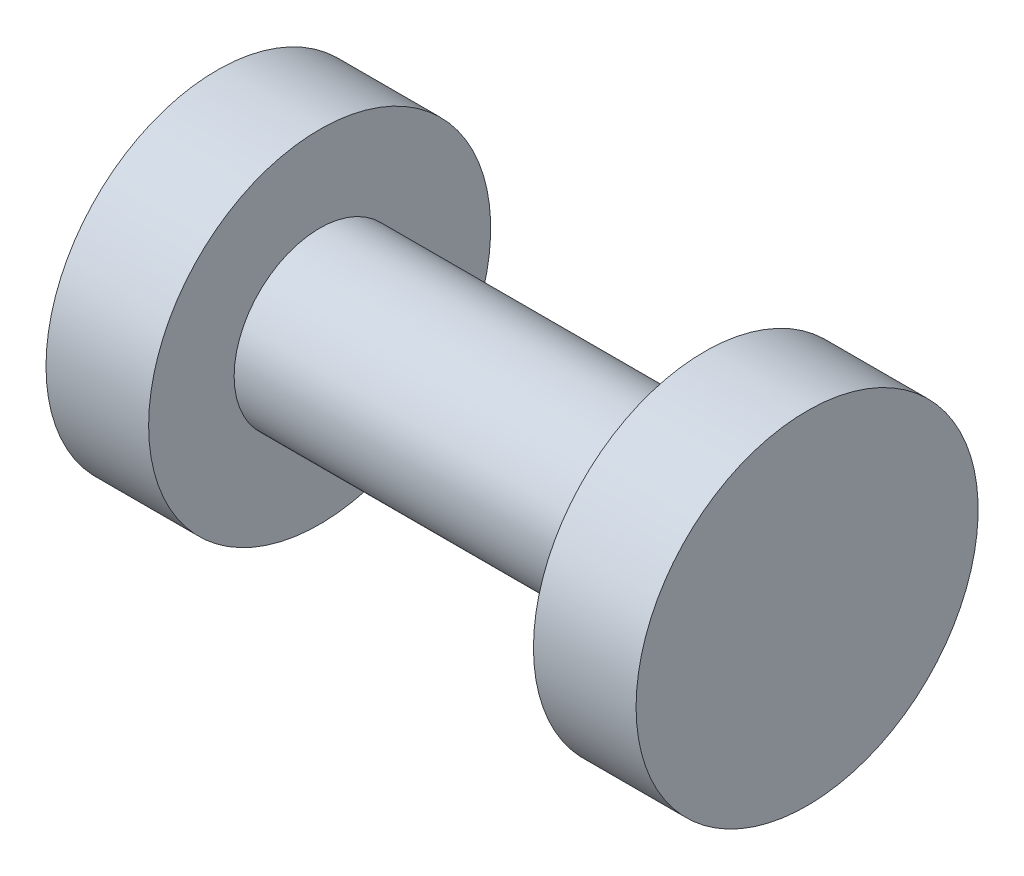
SolidWorks part; units mm, degrees
ref_plane "Front Plane" through (0, 0, 0) normal (0, 0, 1) x (1, 0, 0)
ref_plane "Top Plane" through (0, 0, 0) normal (0, 1, 0) x (1, 0, 0)
ref_plane "Right Plane" through (0, 0, 0) normal (1, 0, 0) x (0, 0, -1)
sketch "Sketch1" plane through (0, 0, 0) normal (0, 1, 0) x (1, 0, 0)
  line L0 (-10.9538, 6.35) -> (-7.1437, 6.35)
  line L1 (-7.1437, 6.35) -> (-7.1438, 3.175)
  line L2 (-7.1438, 3.175) -> (7.1438, 3.175)
  line L3 (7.1438, 3.175) -> (7.1437, 6.35)
  line L4 (7.1437, 6.35) -> (10.9537, 6.35)
  line L5 (10.9537, 6.35) -> (10.9538, 0)
  line L11 (-10.9537, 0) -> (-10.9538, 6.35)
  line L12 (-10.9537, 0) -> (10.9538, 0) construction
  line L13 (10.9538, 0) -> (-10.9537, 0)
  point P8 (0, 3.175)
  dimension "D1" = 6.35
  dimension "D2" = 14.2875
  dimension "D3" = 3.81
  dimension "D4" = 3.175
revolve "Revolve1" add sketch "Sketch1" angle 360 about L12
